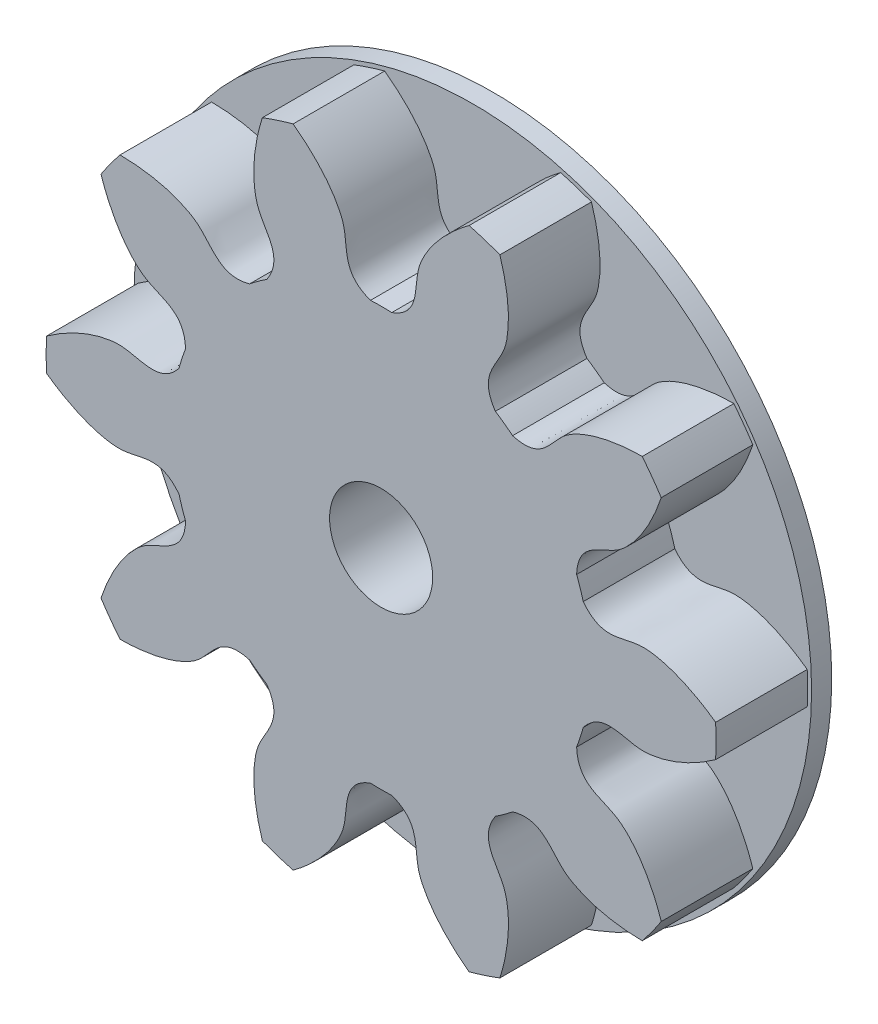
SolidWorks part; units mm, degrees
material "尼龙 6/10"
ref_plane "前视基准面" through (0, 0, 0) normal (0, 0, 1) x (1, 0, 0)
ref_plane "上视基准面" through (0, 0, 0) normal (0, 1, 0) x (1, 0, 0)
ref_plane "右视基准面" through (0, 0, 0) normal (1, 0, 0) x (0, 0, -1)
sketch "草图1" plane through (0, 0, 0) normal (0, 0, 1) x (1, 0, 0)
  circle A0 centre (0, 0) radius 4.2
extrude "凸台-拉伸1" add sketch "草图1" along normal blind 1.1486
ref_axis "基准轴1" through (0, 0, -1.5) along (0, 0, 1)
sketch "草图2" plane through (0, 0, 0) normal (0, 0, 1) x (1, 0, 0)
  line L0 (0, 0) -> (0, 4.2) construction
  circle A0 centre (0, 0) radius 4.2 construction
  arc A1 (0.1333, 2.6216) -> (-0.1333, 2.6216) centre (0, 0) ccw
  arc A2 (2.9775, 4.686) -> (-2.9775, 4.686) centre (0, 0) ccw
  spline S0 degree 3 poles (0.1333, 2.6216) (0.5078, 2.7584) (0.4017, 3.0594) (0.4821, 3.3073) (0.4862, 3.3191) (0.4909, 3.332) (0.4964, 3.3461) (0.5028, 3.3613) (0.5099, 3.3776) (0.5179, 3.3949) (0.5268, 3.4132) (0.5367, 3.4326) (0.5476, 3.4528) (0.5596, 3.474) (0.5726, 3.4961) (0.5868, 3.5191) (0.6021, 3.5429) (0.6186, 3.5674) (0.6364, 3.5927) (0.6555, 3.6187) (0.6759, 3.6453) (0.6976, 3.6726) (0.7207, 3.7004) (0.7453, 3.7288) (0.7712, 3.7576) (0.7987, 3.7869) (0.8276, 3.8166) (0.8581, 3.8466) (0.8901, 3.8769) (0.9237, 3.9074) (0.9588, 3.9381) (0.9956, 3.969) (1.0341, 3.9999) (1.0741, 4.0309) (1.1159, 4.0618) (1.1593, 4.0927) (1.2045, 4.1234) (1.2513, 4.154) (1.2998, 4.1843) (1.3501, 4.2143) (1.4021, 4.2439) (1.4559, 4.2731) (1.5114, 4.3019) (1.5686, 4.3301) (1.6276, 4.3577) (1.6883, 4.3846) (1.7508, 4.4109) (1.815, 4.4364) (1.8809, 4.461) (1.9486, 4.4848) (2.0179, 4.5076) (2.089, 4.5294) (2.1617, 4.5502) (2.2361, 4.5698) (2.3122, 4.5883) (2.3899, 4.6055) (2.4693, 4.6214) (2.5502, 4.6359) (2.6327, 4.6491) (2.7167, 4.6607) (2.8317, 4.6743) (2.9189, 4.682) (2.9775, 4.686) knots 0 0 0 0 0.201721 0.204697 0.208023 0.211699 0.215726 0.220102 0.224829 0.229906 0.235332 0.241109 0.247237 0.253714 0.260541 0.267719 0.275246 0.283124 0.291352 0.29993 0.308858 0.318136 0.327765 0.337743 0.348072 0.358751 0.36978 0.381158 0.392888 0.404967 0.417396 0.430176 0.443305 0.456785 0.470615 0.484795 0.499325 0.514205 0.529435 0.545016 0.560946 0.577227 0.593858 0.610839 0.62817 0.645851 0.663882 0.682264 0.700995 0.720077 0.739509 0.759291 0.779423 0.799905 0.820737 0.84192 0.863452 0.885335 0.907568 0.930151 0.953084 1 1 1 1
  spline S1 degree 3 poles (-0.1333, 2.6216) (-0.5078, 2.7584) (-0.4017, 3.0594) (-0.4821, 3.3073) (-0.4862, 3.3191) (-0.4909, 3.332) (-0.4964, 3.3461) (-0.5028, 3.3613) (-0.5099, 3.3776) (-0.5179, 3.3949) (-0.5268, 3.4132) (-0.5367, 3.4326) (-0.5476, 3.4528) (-0.5596, 3.474) (-0.5726, 3.4961) (-0.5868, 3.5191) (-0.6021, 3.5429) (-0.6186, 3.5674) (-0.6364, 3.5927) (-0.6555, 3.6187) (-0.6759, 3.6453) (-0.6976, 3.6726) (-0.7207, 3.7004) (-0.7453, 3.7288) (-0.7712, 3.7576) (-0.7987, 3.7869) (-0.8276, 3.8166) (-0.8581, 3.8466) (-0.8901, 3.8769) (-0.9237, 3.9074) (-0.9588, 3.9381) (-0.9956, 3.969) (-1.0341, 3.9999) (-1.0741, 4.0309) (-1.1159, 4.0618) (-1.1593, 4.0927) (-1.2045, 4.1234) (-1.2513, 4.154) (-1.2998, 4.1843) (-1.3501, 4.2143) (-1.4021, 4.2439) (-1.4559, 4.2731) (-1.5114, 4.3019) (-1.5686, 4.3301) (-1.6276, 4.3577) (-1.6883, 4.3846) (-1.7508, 4.4109) (-1.815, 4.4364) (-1.8809, 4.461) (-1.9486, 4.4848) (-2.0179, 4.5076) (-2.089, 4.5294) (-2.1617, 4.5502) (-2.2361, 4.5698) (-2.3122, 4.5883) (-2.3899, 4.6055) (-2.4693, 4.6214) (-2.5502, 4.6359) (-2.6327, 4.6491) (-2.7167, 4.6607) (-2.8317, 4.6743) (-2.9189, 4.682) (-2.9775, 4.686) knots 0 0 0 0 0.201721 0.204697 0.208023 0.211699 0.215726 0.220102 0.224829 0.229906 0.235332 0.241109 0.247237 0.253714 0.260541 0.267719 0.275246 0.283124 0.291352 0.29993 0.308858 0.318136 0.327765 0.337743 0.348072 0.358751 0.36978 0.381158 0.392888 0.404967 0.417396 0.430176 0.443305 0.456785 0.470615 0.484795 0.499325 0.514205 0.529435 0.545016 0.560946 0.577227 0.593858 0.610839 0.62817 0.645851 0.663882 0.682264 0.700995 0.720077 0.739509 0.759291 0.779423 0.799905 0.820737 0.84192 0.863452 0.885335 0.907568 0.930151 0.953084 1 1 1 1
extrude "切除-拉伸1" cut sketch "草图2" along normal through all
pattern_circular "阵列(圆周)1" count 10 over 360 about axis through (0, 0, -1.5) along (0, 0, 1) of "切除-拉伸1"
sketch "草图3" plane through (0, 0, 0) normal (0, 0, 1) x (1, 0, 0)
  circle A0 centre (0, 0) radius 3.5 construction
  dimension "Dn" = 7
sketch "草图4" plane through (0, 0, 1.1486) normal (0, 0, 1) x (1, 0, 0)
  circle A0 centre (0, 0) radius 2.25
  dimension "D1" = 4.5
scale "缩放比例1" scale about centroid uniform scaling yes scale factor 0.870588
sketch "草图5" plane through (0, 0, 1.0743) normal (0, 0, 1) x (1, 0, 0)
  circle A0 centre (0, 0) radius 0.5625
  dimension "D1" = 1.125
extrude "切除-拉伸2" cut sketch "草图5" against normal through all
sketch "草图7" plane through (0, 0, 0.0743) normal (0, 0, -1) x (-1, 0, 0)
  circle A0 centre (0, 0) radius 3.7
  dimension "D1" = 7.4
extrude "凸台-拉伸3" add sketch "草图7" along normal blind 0.22
sketch "草图8" plane through (0, 0, 1.0743) normal (0, 0, 1) x (1, 0, 0)
  circle A0 centre (0, 0) radius 0.5625 construction
  circle A1 centre (0, 0) radius 0.5625
extrude "切除-拉伸3" cut sketch "草图8" against normal through all
